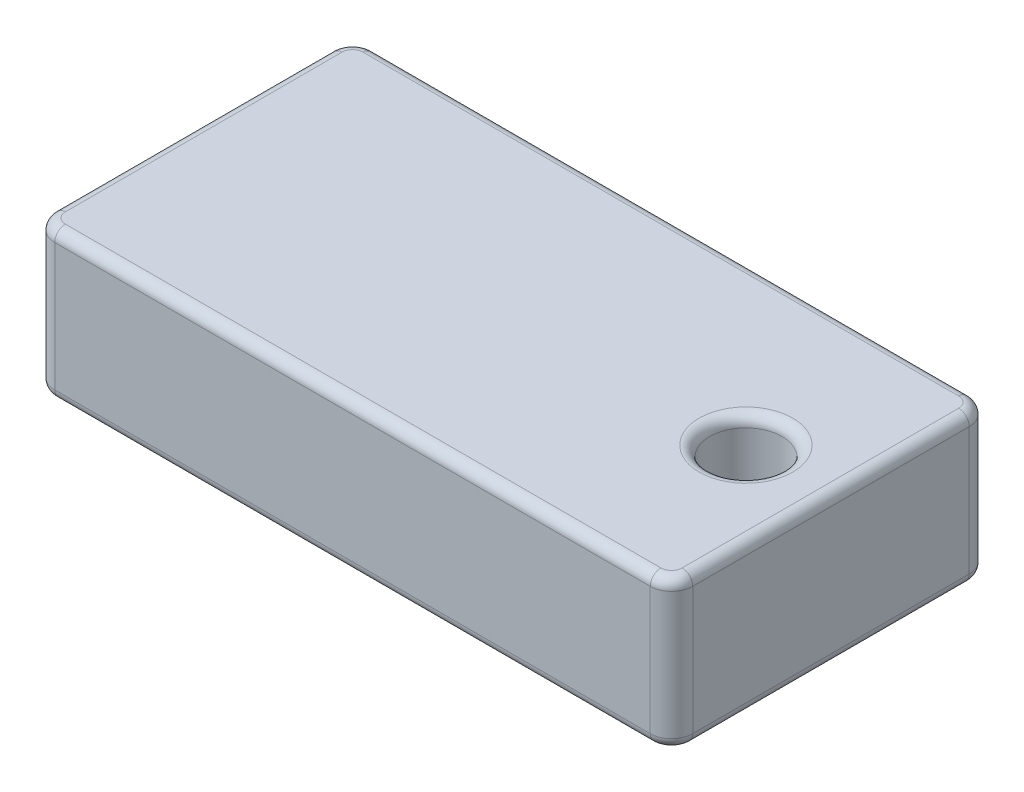
SolidWorks part; units mm, degrees
material "PE(聚乙烯)"
ref_plane "前视基准面" through (0, 0, 0) normal (0, 0, 1) x (1, 0, 0)
ref_plane "上视基准面" through (0, 0, 0) normal (0, 1, 0) x (1, 0, 0)
ref_plane "右视基准面" through (0, 0, 0) normal (1, 0, 0) x (0, 0, -1)
other "Configuration Table"
sketch "草图1" plane through (0, 0, 0) normal (0, 1, 0) x (1, 0, 0)
  line L1 (-15, 7.5) -> (15, 7.5)
  line L2 (-15, 7.5) -> (-15, -7.5)
  line L3 (-15, -7.5) -> (15, -7.5)
  line L4 (15, 7.5) -> (15, -7.5)
  line L5 (-15, 7.5) -> (15, -7.5) construction
  line L6 (-15, -7.5) -> (15, 7.5) construction
  point P0 (0, 0)
  dimension "D1" = 30
  dimension "D2" = 15
extrude "凸台-拉伸1" add sketch "草图1" along normal blind 7
hole_wizard "M3 间隙孔1" positions "草图2" profile "草图3" hole size "M3" standard "GB" end condition through all
sketch "草图2" plane through (0, 7, 0) normal (0, 1, 0) x (1, 0, 0)
  line L0 (15, -7.5) -> (15, 7.5) construction
  point P0 (11, 0)
  dimension "D1" = 4
sketch "草图3" plane through (11, 7, 0) normal (1, 0, 0) x (0, 0, 1)
  line L0 (0, 0) -> (0, 7)
  line L1 (0, 7) -> (1.7, 7)
  line L2 (1.7, 7) -> (1.7, 0)
  line L5 (1.7, 0) -> (0, 0)
  line L11 (0, -6.35) -> (0, 107.95) construction
  dimension "通孔孔直径" = 3.4
  dimension "通孔孔深度" = 7
fillet "圆角1" radius 1 4 edges at (-15, 3.5, -7.5) (15, 3.5, -7.5) (15, 3.5, 7.5) (-15, 3.5, 7.5)
fillet "圆角2" radius 0.5 18 edges at (-14.7071, 0, 7.2071) (0, 0, 7.5) (14.7071, 0, 7.2071) (15, 0, 0) (14.7071, 0, -7.2071) (0, 0, -7.5) (-14.7071, 0, -7.2071) (-15, 0, 0) (11, 0, 1.7) (14.7071, 7, -7.2071) (15, 7, 0) (14.7071, 7, 7.2071) (0, 7, 7.5) (-14.7071, 7, 7.2071) (-15, 7, 0) (-14.7071, 7, -7.2071) (0, 7, -7.5) (11, 7, 1.7)
sketch "草图4" plane through (0, 0, -7.5) normal (0, 0, -1) x (-1, 0, 0)
  line L1 (7.3827, 5.819) -> (12.1487, 5.819)
  line L2 (7.3827, 5.819) -> (7.3827, 5.414)
  line L3 (7.3827, 5.414) -> (12.1487, 5.414)
  line L4 (12.1487, 5.819) -> (12.1487, 5.414)
extrude "切除-拉伸1" cut sketch "草图4" against normal blind 3
